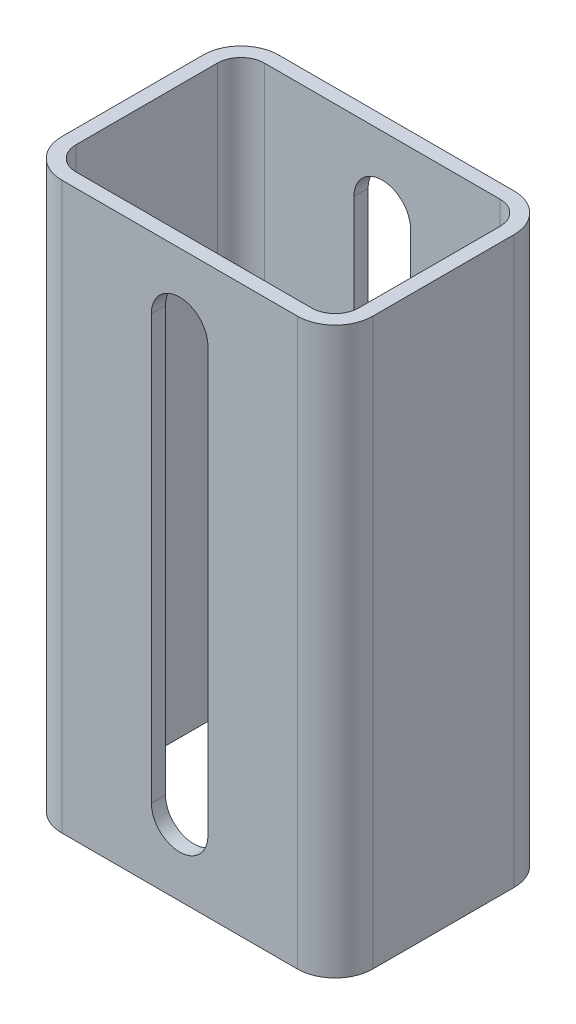
SolidWorks part; units mm, degrees
ref_plane "Front Plane" through (0, 0, 0) normal (0, 0, 1) x (1, 0, 0)
ref_plane "Top Plane" through (0, 0, 0) normal (0, 1, 0) x (1, 0, 0)
ref_plane "Right Plane" through (0, 0, 0) normal (1, 0, 0) x (0, 0, -1)
sketch "Sketch1" plane through (0, 0, 0) normal (0, 1, 0) x (1, 0, 0)
  line L1 (-25, -20) -> (25, -20)
  line L2 (-30, -15) -> (-30, 15)
  line L3 (-25, 20) -> (25, 20)
  line L4 (30, -15) -> (30, 15)
  line L5 (-30, -20) -> (30, 20) construction
  line L6 (-30, 20) -> (30, -20) construction
  arc A0 (25, -20) -> (30, -15) centre (25, -15) ccw
  arc A1 (-25, -20) -> (-30, -15) centre (-25, -15) cw
  arc A2 (-30, 15) -> (-25, 20) centre (-25, 15) cw
  arc A3 (25, 20) -> (30, 15) centre (25, 15) cw
  point P0 (0, 0)
  dimension "D3" = 5
  dimension "D1" = 60
  dimension "D2" = 40
extrude "Extrude-Thin1" add sketch "Sketch1" along normal mid plane 120 thin thin type one direction wall 3
sketch "Sketch2" plane through (0, 0, 23) normal (0, 0, 1) x (1, 0, 0)
  line L0 (0, 45) -> (0, -45) construction
  line L1 (6, 45) -> (6, -45)
  line L2 (-6, 45) -> (-6, -45)
  line L3 (-25, 0) -> (25, 0) construction
  line L4 (-25, 60) -> (-25, -60) construction
  line L5 (25, 60) -> (25, -60) construction
  arc A0 (6, 45) -> (-6, 45) centre (0, 45) ccw
  arc A1 (-6, -45) -> (6, -45) centre (0, -45) ccw
  point P3 (0, 0)
  point P14 (0, 0)
  dimension "D1" = 6
  dimension "D2" = 90
extrude "Cut-Extrude1" cut sketch "Sketch2" against normal through all both and the other way through all
